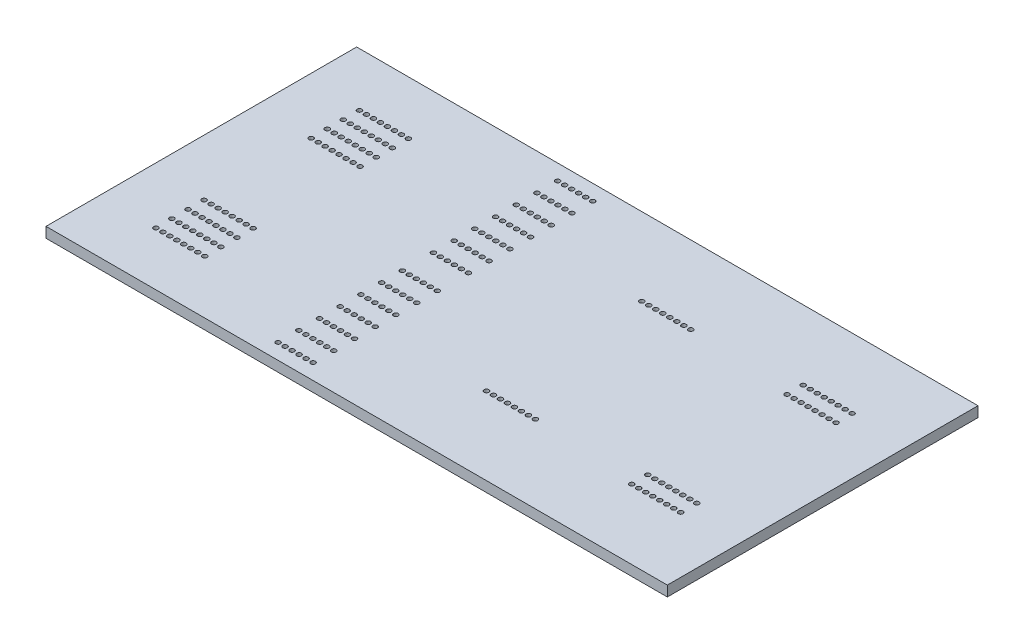
SolidWorks part; units mm, degrees
ref_plane "Plan de face" through (0, 0, 0) normal (0, 0, 1) x (1, 0, 0)
ref_plane "Plan de dessus" through (0, 0, 0) normal (0, 1, 0) x (1, 0, 0)
ref_plane "Plan de droite" through (0, 0, 0) normal (1, 0, 0) x (0, 0, -1)
sketch "Esquisse2" plane through (0, 0, 0) normal (0, 1, 0) x (1, 0, 0)
  line L1 (-60, -15) -> (60, -15)
  line L2 (-60, -15) -> (-60, 15)
  line L3 (-60, 15) -> (60, 15)
  line L4 (60, -15) -> (60, 15)
  line L5 (-60, -15) -> (60, 15) construction
  line L6 (-60, 15) -> (60, -15) construction
  point P0 (0, 0)
  dimension "D1" = 30
  dimension "D2" = 120
extrude "Boss.-Extru.1" add sketch "Esquisse2" along normal blind 2 contours L3 L4 L1 L2
sketch "Cavités" plane through (0, 0, 0) normal (0, 1, 0) x (1, 0, 0)
  line L0 (-60, -15) -> (60, -15) construction
  line L1 (-58.4, 15) -> (-30.4, 15) construction
  line L2 (-58.4, 15) -> (-58.4, -15) construction
  line L3 (-58.4, -15) -> (-30.4, -15) construction
  line L4 (-30.4, 15) -> (-30.4, -15) construction
  line L5 (-60, 15) -> (60, 15) construction
  line L6 (-28.8, 15) -> (-0.8, 15) construction
  line L7 (-28.8, 15) -> (-28.8, -15) construction
  line L8 (-28.8, -15) -> (-0.8, -15) construction
  line L9 (-0.8, 15) -> (-0.8, -15) construction
  line L10 (-30.4, 15) -> (-28.8, 15) construction
  line L11 (0.8, 15) -> (28.8, 15) construction
  line L12 (0.8, 15) -> (0.8, -15) construction
  line L13 (0.8, -15) -> (28.8, -15) construction
  line L14 (28.8, 15) -> (28.8, -15) construction
  line L15 (30.4, 15) -> (58.4, 15) construction
  line L16 (30.4, 15) -> (30.4, -15) construction
  line L17 (30.4, -15) -> (58.4, -15) construction
  line L18 (58.4, 15) -> (58.4, -15) construction
  line L19 (-0.8, 15) -> (0.8, 15) construction
  line L20 (28.8, 15) -> (30.4, 15) construction
  line L21 (-60, 15) -> (-58.4, 15) construction
  line L22 (58.4, 15) -> (60, 15) construction
  dimension "D1" = 28
  dimension "D2" = 1.6
sketch "Esquisse7" plane through (0, 2, 0) normal (0, 1, 0) x (1, 0, 0)
  line L0 (-58.4, 0) -> (-49.125, 0) construction
  line L1 (-49.125, 4.6665) -> (-39.675, 4.6665) construction
  line L2 (-49.125, 4.6665) -> (-49.125, -4.6665) construction
  line L3 (-49.125, -4.6665) -> (-39.675, -4.6665) construction
  line L4 (-39.675, 4.6665) -> (-39.675, -4.6665) construction
  line L5 (-58.4, 15) -> (-58.4, -15) construction
  line L6 (-39.675, 0) -> (-30.4, 0) construction
  line L7 (-30.4, 15) -> (-30.4, -15) construction
  dimension "D1" = 9.45
  dimension "D2" = 9.333
sketch "Esquisse8" plane through (0, 2, 0) normal (0, 1, 0) x (1, 0, 0)
  circle A0 centre (-49.125, 4.6665) radius 0.45
  dimension "D1" = 0.9
extrude "Enlèv. mat.-Extru.3" cut sketch "Esquisse8" against normal up to next
pattern_linear "Répétition linéaire4" count 8 spacing 1.35 along (1, 0, 0) count 4 spacing 3.111 along (0, 0, 1) of "Enlèv. mat.-Extru.3"
sketch "Esquisse9" plane through (0, 2, 0) normal (0, 1, 0) x (1, 0, 0)
  line L0 (-28.8, 0) -> (-18.175, 0) construction
  line L1 (-18.175, 12) -> (-11.425, 12) construction
  line L2 (-18.175, 12) -> (-18.175, -12) construction
  line L3 (-18.175, -12) -> (-11.425, -12) construction
  line L4 (-11.425, 12) -> (-11.425, -12) construction
  line L5 (-28.8, 15) -> (-28.8, -15) construction
  line L6 (-11.425, 0) -> (-0.8, 0) construction
  line L7 (-0.8, 15) -> (-0.8, -15) construction
  dimension "D1" = 6.75
  dimension "D2" = 24
sketch "Esquisse10" plane through (0, 2, 0) normal (0, 1, 0) x (1, 0, 0)
  circle A0 centre (-18.175, 12) radius 0.45
  dimension "D1" = 0.9
extrude "Enlèv. mat.-Extru.4" cut sketch "Esquisse10" against normal up to next
pattern_linear "Répétition linéaire5" count 6 spacing 1.35 along (1, 0, 0) count 7 spacing 4 along (0, 0, 1) of "Enlèv. mat.-Extru.4"
sketch "Esquisse11" plane through (0, 2, 0) normal (0, 1, 0) x (1, 0, 0)
  line L0 (0.8, 0) -> (10.075, 0) construction
  line L5 (0.8, 15) -> (0.8, -15) construction
  line L6 (19.525, 0) -> (28.8, 0) construction
  line L7 (28.8, 15) -> (28.8, -15) construction
  line L8 (10.075, 0) -> (19.525, 0) construction
  dimension "D1" = 9.45
sketch "Esquisse12" plane through (0, 2, 0) normal (0, 1, 0) x (1, 0, 0)
  circle A0 centre (10.075, 0) radius 0.45
  dimension "D1" = 0.9
extrude "Enlèv. mat.-Extru.5" cut sketch "Esquisse12" against normal up to next
pattern_linear "Répétition linéaire6" count 8 spacing 1.35 along (1, 0, 0) of "Enlèv. mat.-Extru.5"
sketch "Esquisse13" plane through (0, 2, 0) normal (0, 1, 0) x (1, 0, 0)
  line L0 (30.4, 0) -> (39.675, 0) construction
  line L1 (39.675, 1.555) -> (49.125, 1.555) construction
  line L2 (39.675, 1.555) -> (39.675, -1.555) construction
  line L3 (39.675, -1.555) -> (49.125, -1.555) construction
  line L4 (49.125, 1.555) -> (49.125, -1.555) construction
  line L5 (30.4, 15) -> (30.4, -15) construction
  line L6 (49.125, 0) -> (58.4, 0) construction
  line L7 (58.4, 15) -> (58.4, -15) construction
  dimension "D1" = 3.11
  dimension "D2" = 9.45
sketch "Esquisse14" plane through (0, 2, 0) normal (0, 1, 0) x (1, 0, 0)
  circle A0 centre (39.675, 1.555) radius 0.45
  dimension "D1" = 0.9
extrude "Enlèv. mat.-Extru.6" cut sketch "Esquisse14" against normal up to next
pattern_linear "Répétition linéaire7" count 8 spacing 1.35 along (1, 0, 0) count 2 spacing 3.11 along (0, 0, 1) of "Enlèv. mat.-Extru.6"
mirror "Symétrie1" about plane through (-60, 2, 15) normal (0, 0, -1) of bodies 114
